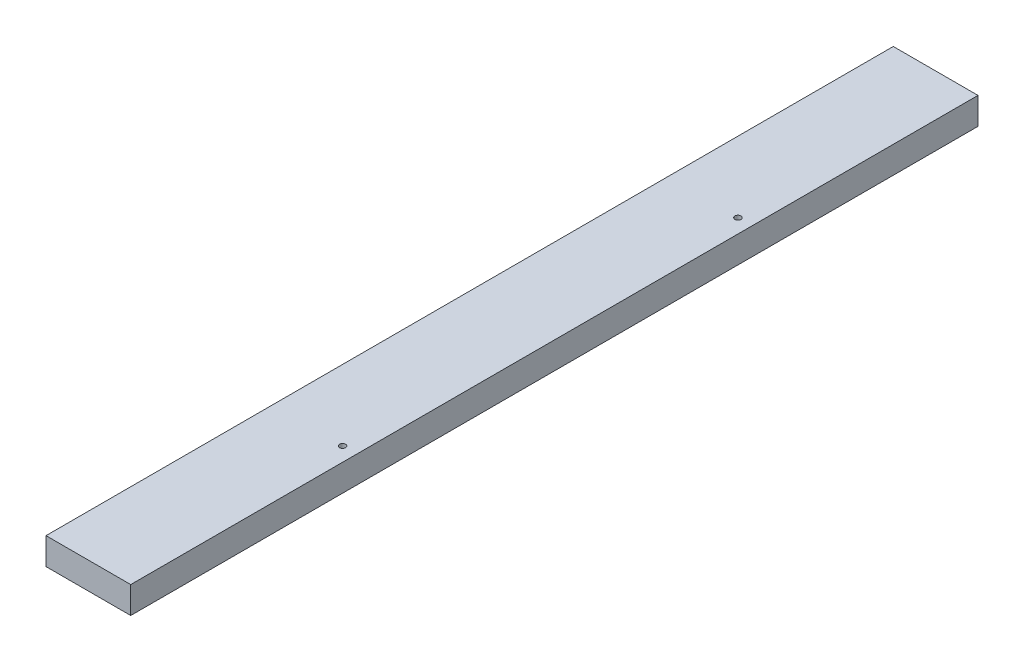
SolidWorks part; units mm, degrees
ref_plane "Płaszczyzna przednia" through (0, 0, 0) normal (0, 0, 1) x (1, 0, 0)
ref_plane "Płaszczyzna górna" through (0, 0, 0) normal (0, 1, 0) x (1, 0, 0)
ref_plane "Płaszczyzna prawa" through (0, 0, 0) normal (1, 0, 0) x (0, 0, -1)
sketch "Sketch1" plane through (0, 0, 0) normal (0, 0, 1) x (1, 0, 0)
  line L1 (0, 0) -> (60, 0)
  line L2 (0, 0) -> (0, 19)
  line L3 (0, 19) -> (60, 19)
  line L4 (60, 0) -> (60, 19)
  line L5 (0, 0) -> (60, 19) construction
  line L6 (0, 19) -> (60, 0) construction
  point P4 (30, 9.5)
  dimension "D1" = 19
  dimension "D2" = 60
extrude "Boss-Extrude1" add sketch "Sketch1" along normal blind 600
sketch "Sketch2" plane through (0, 0, 0) normal (0, -1, 0) x (-1, 0, 0)
  line L0 (0, 0) -> (-60, 0) construction
  line L1 (0, -600) -> (0, 0) construction
  line L2 (0, -600) -> (-60, -600) construction
  circle A0 centre (-38, -10) radius 2.5
  circle A1 centre (-38, -590) radius 2.5
  dimension "D1" = 10
  dimension "D2" = 38
  dimension "D3" = 5
  dimension "D4" = 5
  dimension "D5" = 10
  dimension "D6" = 38
extrude "Cut-Extrude1" cut sketch "Sketch2" against normal blind 10
sketch "Sketch3" plane through (0, 0, 0) normal (0, -1, 0) x (1, 0, 0)
  line L0 (47.1, 503.6529) -> (47.1, 502.5)
  line L1 (41.3, 550) -> (25.8, 550)
  line L2 (47.1, 543.5) -> (47.1, 503.6529)
  line L3 (47.1, 502.5) -> (20, 502.5)
  line L4 (20, 543.5) -> (20, 508.663)
  line L5 (47.1, 550) -> (20, 502.5) construction
  line L6 (47.1, 502.5) -> (20, 550) construction
  line L7 (20, 502.5) -> (20, 508.663)
  line L8 (0, 600) -> (0, 0) construction
  line L9 (25.8, 550) -> (20, 543.5)
  line L10 (0, 600) -> (60, 600) construction
  line L11 (47.1, 543.5) -> (41.3, 550)
  point P4 (33.55, 526.25)
  dimension "D1" = 47.5
  dimension "D2" = 27.1
  dimension "D3" = 5.8
  dimension "D4" = 6.5
  dimension "D5" = 5.8
  dimension "D6" = 6.5
  dimension "D7" = 20
  dimension "D8" = 50
extrude "Cut-Extrude2" [suppressed] cut sketch "Sketch3" against normal through all
sketch "Sketch4" [suppressed] plane through (0, 0, 0) normal (0, -1, 0) x (-1, 0, 0)
  line L0 (0, -600) -> (-60, -600) construction
  line L1 (-60, 0) -> (-60, -600) construction
  line L3 (0, -600) -> (0, 0) construction
  circle A0 centre (-53.55, -525.15) radius 1.8
  circle A1 centre (-13.55, -525.15) radius 1.8
  dimension "D1" = 3.6
  dimension "D2" = 3.6
  dimension "D3" = 74.85
  dimension "D4" = 74.85
  dimension "D5" = 6.45
  dimension "D6" = 13.55
extrude "Cut-Extrude3" [suppressed] cut sketch "Sketch4" against normal blind 13
hole_wizard "CSK for M4 Flat Head Machine Screw1" positions "Sketch6" profile "Sketch7" countersink size "M4" standard "ANSI Metric" end condition through all
sketch "Sketch6" plane through (0, 0, 0) normal (0, -1, 0) x (-1, 0, 0)
  line L0 (-60, -600) -> (-60, 0) construction
  line L2 (0, 0) -> (-60, 0) construction
  line L3 (0, -600) -> (-60, -600) construction
  point P0 (-50, -160)
  point P2 (-50, -440)
  dimension "D1" = 10
  dimension "D2" = 160
  dimension "D3" = 10
  dimension "D4" = 160
sketch "Sketch7" plane through (50, 0, 160) normal (1, 0, 0) x (0, 0, -1)
  line L0 (0, 0) -> (0, 19)
  line L1 (0, 19) -> (2.15, 19)
  line L2 (2.15, 19) -> (2.15, 2.55)
  line L3 (2.15, 2.55) -> (4.7, 0)
  line L5 (4.7, 0) -> (0, 0)
  line L6 (-2.15, 2.55) -> (-4.7, 0) construction
  line L11 (0, -6.35) -> (0, 107.95) construction
  dimension "Thru Hole Dia." = 4.3
  dimension "Thru Hole Depth" = 19
  dimension "Near C'Sink Dia." = 9.4
  dimension "Near C'Sink Angle" = 90
